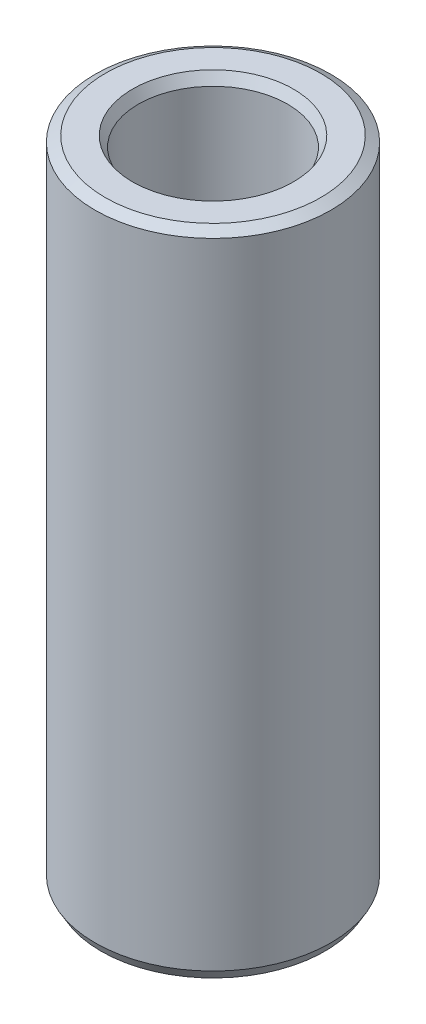
SolidWorks part; units mm, degrees
ref_plane "Front Plane" through (0, 0, 0) normal (0, 0, 1) x (1, 0, 0)
ref_plane "Top Plane" through (0, 0, 0) normal (0, 1, 0) x (1, 0, 0)
ref_plane "Right Plane" through (0, 0, 0) normal (1, 0, 0) x (0, 0, -1)
sketch "Sketch1" plane through (0, 0, 0) normal (0, 1, 0) x (1, 0, 0)
  circle A0 centre (0, 0) radius 10
  dimension "SLEEVE_OD" = 20
extrude "Boss-Extrude1" add sketch "Sketch1" along normal blind 55.1978
sketch "Sketch2" plane through (0, 0, 0) normal (0, 1, 0) x (1, 0, 0)
  circle A0 centre (0, 0) radius 6.3305
  dimension "BORE_D" = 12.6611
extrude "Cut-Extrude1" cut sketch "Sketch2" along normal through all
chamfer "Chamfer1" distance 0.4973 angle 60 4 edges at (0, 55.1978, 6.3305) (0, 0, 6.3305) (0, 0, 10) (0, 55.1978, 10) first distance on face at (0, 55.1978, 6.3305) first distance on face at (0, 0, 6.3305) first distance on face at (0, 55.1978, 10)
